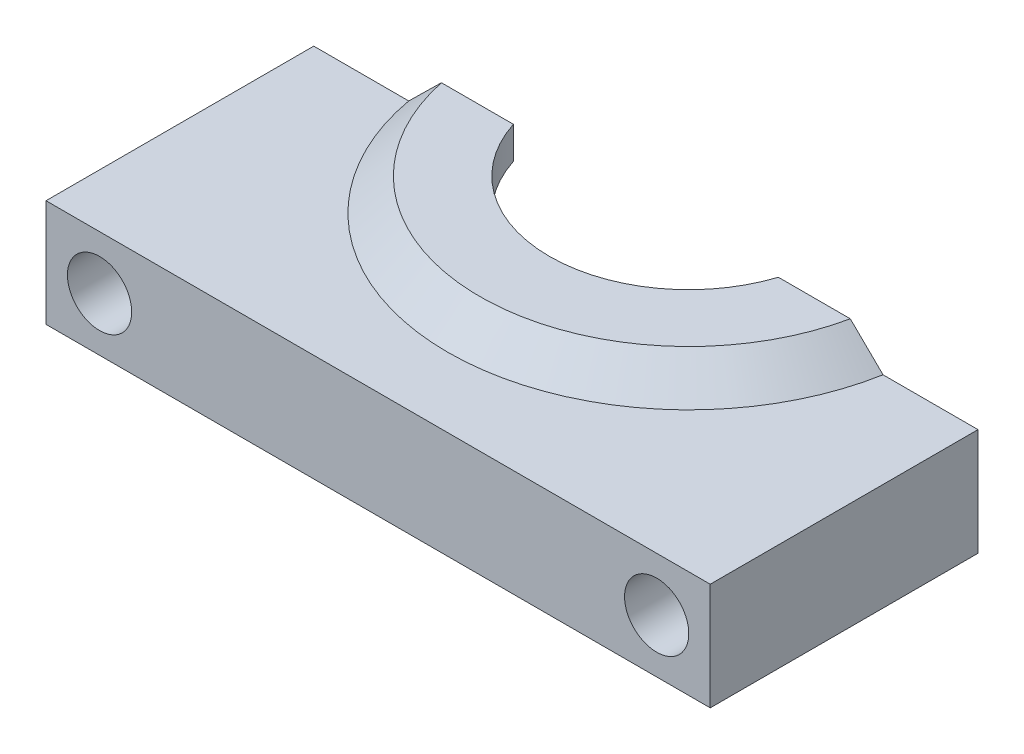
SolidWorks part; units mm, degrees
material "6061 Alloy"
ref_plane "Front Plane" through (0, 0, 0) normal (0, 0, 1) x (1, 0, 0)
ref_plane "Top Plane" through (0, 0, 0) normal (0, 1, 0) x (1, 0, 0)
ref_plane "Right Plane" through (0, 0, 0) normal (1, 0, 0) x (0, 0, -1)
sketch "Sketch1" plane through (0, 0, 0) normal (0, 1, 0) x (1, 0, 0)
  line L0 (-16.3066, -4) -> (-31.0078, -4)
  line L3 (22, -29) -> (-22, -29)
  line L6 (-31.0078, -4) -> (-31.0078, -29)
  line L7 (-31.0078, -29) -> (-22, -29)
  line L8 (16.3066, -4) -> (31.0078, -4)
  line L9 (31.0078, -4) -> (31.0078, -29)
  line L10 (31.0078, -29) -> (22, -29)
  arc A1 (-16.3066, -4) -> (16.3066, -4) centre (0, 0) ccw
extrude "Boss-Extrude1" add sketch "Sketch1" along normal blind 10
sketch "Sketch2" plane through (0, 0, 4) normal (0, 0, -1) x (-1, 0, 0)
  line L0 (-31.0078, 5) -> (-26.0078, 5) construction
  line L3 (-31.0078, 10) -> (-31.0078, 0) construction
  line L6 (31.0078, 5) -> (26.0078, 5) construction
  line L7 (31.0078, 10) -> (31.0078, 0) construction
  circle A2 centre (-26.0078, 5) radius 3
  circle A3 centre (26.0078, 5) radius 3
extrude "Cut-Extrude1" cut sketch "Sketch2" against normal blind 27
sketch "Sketch4" plane through (0, 10, 0) normal (0, 1, 0) x (1, 0, 0)
  circle A0 centre (0, 0) radius 13
  circle A1 centre (0, 0) radius 19.5
  dimension "D1" = 39
extrude "Boss-Extrude2" add sketch "Sketch4" along normal blind 3
sketch "Sketch5" plane through (0, 13, 0) normal (0, 1, 0) x (1, 0, 0)
  line L0 (-19.0853, -4) -> (-23.6257, -4)
  line L1 (-19.0853, -4) -> (25.4099, -4)
  line L4 (25.4099, -4) -> (25.4099, 24.1135)
  line L5 (-19.0853, -4) -> (-31.0078, -4) construction
  line L6 (-23.6257, -4) -> (-23.6257, 24.1135)
  line L7 (-23.6257, 24.1135) -> (25.4099, 24.1135)
extrude "Cut-Extrude2" cut sketch "Sketch5" against normal blind 8
chamfer "Chamfer1" distance 3 angle 45 1 edges at (0, 10, 19.5)
sketch "Sketch6" plane through (0, 0, 0) normal (0, -1, 0) x (1, 0, 0)
  line L0 (0, 29) -> (0, 16.79) construction
  line L1 (-31.0078, 29) -> (31.0078, 29) construction
  line L3 (-20.7181, 19.3309) -> (20.7181, 19.3309)
  line L4 (-20.7181, 19.3309) -> (-20.7181, 26.4591)
  line L5 (-20.7181, 26.4591) -> (20.7181, 26.4591)
  line L6 (20.7181, 19.3309) -> (20.7181, 26.4591)
  line L7 (-20.7181, 19.3309) -> (20.7181, 26.4591) construction
  line L8 (-20.7181, 26.4591) -> (20.7181, 19.3309) construction
  arc A0 (16.3066, 4) -> (-16.3066, 4) centre (0, 0) ccw construction
  point P7 (0, 22.895)
extrude "Cut-Extrude3" cut sketch "Sketch6" against normal blind 5
fillet "Fillet1" radius 3.65 4 edges at (-20.7181, 2.5, 19.3309) (-20.7181, 2.5, 26.4591) (20.7181, 2.5, 26.4591) (20.7181, 2.5, 19.3309)
